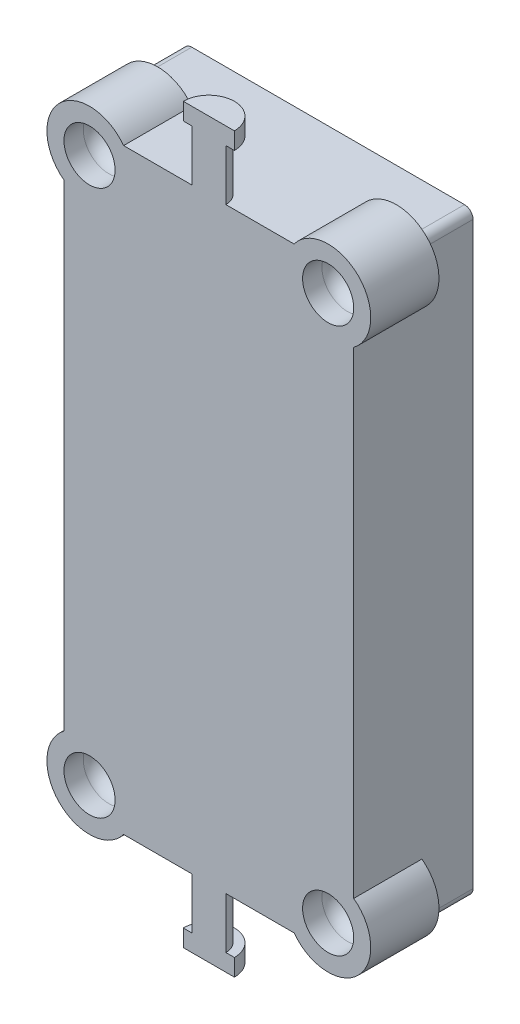
SolidWorks part; units mm, degrees
ref_plane "Front Plane" through (0, 0, 0) normal (0, 0, 1) x (1, 0, 0)
ref_plane "Top Plane" through (0, 0, 0) normal (0, 1, 0) x (1, 0, 0)
ref_plane "Right Plane" through (0, 0, 0) normal (1, 0, 0) x (0, 0, -1)
sketch "Sketch1" plane through (0, 0, 0) normal (0, 0, 1) x (1, 0, 0)
  line L5 (0, 0) -> (34, 0)
  line L6 (0, 0) -> (0, 70)
  line L7 (0, 70) -> (34, 70)
  line L8 (34, 0) -> (34, 70)
  dimension "D1" = 34
  dimension "D2" = 70
extrude "Boss-Extrude1" add sketch "Sketch1" along normal blind 14
sketch "Sketch2" plane through (0, 0, 0) normal (0, 0, -1) x (-1, 0, 0)
  line L0 (-34, 70) -> (0, 70) construction
  line L1 (-32, 68) -> (-2, 68)
  line L2 (-32, 68) -> (-32, 2)
  line L3 (-32, 2) -> (-2, 2)
  line L4 (-2, 68) -> (-2, 2)
  line L5 (0, 70) -> (0, 0) construction
  line L6 (-34, 0) -> (-34, 70) construction
  point P4 (-17, 68)
  point P7 (-17, 70)
  point P8 (-2, 35)
  point P11 (0, 35)
  dimension "D1" = 2
  dimension "D2" = 2
extrude "Cut-Extrude1" cut sketch "Sketch2" against normal offset from surface (12 mm away) 2 up to face at (17, 35, 14)
sketch "Sketch3" plane through (0, 0, 0) normal (0, 0, -1) x (-1, 0, 0)
  line L0 (-34, 70) -> (0, 70) construction
  line L1 (-34, 0) -> (-34, 70) construction
  line L2 (0, 70) -> (0, 0) construction
  line L3 (0, 0) -> (-34, 0) construction
  circle A0 centre (-31, 67) radius 3
  circle A1 centre (-3, 67) radius 3
  circle A2 centre (-3, 3) radius 3
  circle A3 centre (-31, 3) radius 3
  point P16 (0, 0)
  point P17 (0, 0)
  point P18 (0, 0)
  point P19 (0, 0)
  dimension "D1" = 6
  dimension "D2" = 6
  dimension "D3" = 6
  dimension "D4" = 6
extrude "Boss-Extrude2" add sketch "Sketch3" against normal up to surface (12 mm away) up to face at (17, 35, 12)
sketch "Sketch4" plane through (0, 0, 0) normal (0, 0, -1) x (-1, 0, 0)
  circle A0 centre (-3, 67) radius 2
  circle A1 centre (-31, 67) radius 2
  circle A2 centre (-3, 3) radius 2
  circle A3 centre (-31, 3) radius 2
  point P11 (-25.4815, 12.863)
  point P12 (0, 0)
  point P13 (0, 0)
  dimension "D1" = 4
  dimension "D2" = 4
  dimension "D3" = 4
  dimension "D4" = 4
extrude "Cut-Extrude2" cut sketch "Sketch4" against normal through all
sketch "Sketch6" plane through (0, 0, 0) normal (0, -1, 0) x (1, 0, 0)
  line L0 (9.5, 0) -> (24.5, 0) construction
  line L1 (0, 0) -> (34, 0) construction
  circle A0 centre (9.5, 0) radius 2.5
  circle A1 centre (24.5, 0) radius 2
  point P5 (17, 0)
  point P6 (17, 0)
  dimension "D1" = 5
  dimension "D2" = 4
  dimension "D3" = 15
extrude "Cut-Extrude4" cut sketch "Sketch6" against normal up to next
fillet "Fillet1" radius 1 4 edges at (34, 70, 7) (0, 70, 7) (0, 0, 7) (34, 0, 7)
sketch "Sketch7" plane through (0, 0, 14) normal (0, 0, 1) x (1, 0, 0)
  circle A0 centre (31, 67) radius 3
  circle A1 centre (3, 67) radius 3
  circle A2 centre (3, 3) radius 3
  circle A3 centre (31, 3) radius 3
  circle A4 centre (31, 67) radius 5
  circle A5 centre (3, 67) radius 5
  circle A6 centre (31, 3) radius 5
  circle A7 centre (3, 3) radius 5
  dimension "D1" = 6
  dimension "D2" = 6
  dimension "D3" = 6
  dimension "D4" = 6
  dimension "D5" = 10
  dimension "D6" = 10
  dimension "D7" = 10
  dimension "D8" = 10
extrude "Boss-Extrude3" add sketch "Sketch7" against normal offset from surface (8 mm away) 6 up to face at (16.95, 28.2, 0)
sketch "Sketch8" plane through (0, 0, 14) normal (0, 0, 1) x (1, 0, 0)
  circle A0 centre (3, 3) radius 3
  circle A1 centre (31, 3) radius 3
  circle A2 centre (31, 67) radius 3
  circle A4 centre (3, 67) radius 3
  dimension "D1" = 6
  dimension "D2" = 6
  dimension "D3" = 6
  dimension "D4" = 6
extrude "Cut-Extrude7" cut sketch "Sketch8" against normal offset from surface (4 mm away) 10 up to face at (16.95, 28.2, 0)
sketch "Sketch9" plane through (0, 70, 0) normal (0, 1, 0) x (1, 0, 0)
  line L0 (27, -14) -> (7, -14) construction
  line L1 (20, -14) -> (14, -14)
  arc A2 (14, -14) -> (20, -14) centre (17, -14) cw
  dimension "D1" = 3
extrude "Boss-Extrude4" add sketch "Sketch9" along normal blind 8
sketch "Sketch10" plane through (0, 78, 0) normal (0, 1, 0) x (1, 0, 0)
  line L1 (14, -14) -> (20, -14) construction
  line L2 (19, -14) -> (20, -14)
  line L3 (15, -14) -> (14, -14)
  arc A0 (14, -14) -> (20, -14) centre (17, -14) cw
  arc A2 (15, -14) -> (19, -14) centre (17, -14) cw
  dimension "D1" = 1
extrude "Cut-Extrude8" cut sketch "Sketch10" against normal up to surface (8 mm away) from offset 2 up to face at (17, 70, 7.7) offset against normal yes
sketch "Sketch11" plane through (0, 0, 0) normal (0, -1, 0) x (1, 0, 0)
  line L0 (7, 14) -> (27, 14) construction
  line L1 (20, 14) -> (14, 14)
  arc A0 (20, 14) -> (14, 14) centre (17, 14) cw
  dimension "D1" = 3
extrude "Boss-Extrude5" add sketch "Sketch11" along normal blind 8
sketch "Sketch12" plane through (0, -8, 0) normal (0, -1, 0) x (1, 0, 0)
  line L0 (20, 14) -> (14, 14) construction
  line L1 (14, 14) -> (15, 14)
  line L2 (19, 14) -> (20, 14)
  arc A0 (15, 14) -> (19, 14) centre (17, 14) ccw
  arc A1 (20, 14) -> (14, 14) centre (17, 14) cw
  arc A2 (14, 14) -> (20, 14) centre (17, 14) ccw construction
  dimension "D1" = 1
extrude "Cut-Extrude9" cut sketch "Sketch12" against normal up to surface (8 mm away) from offset 2 up to face at (17, 0, 5.8214) offset against normal yes
fillet "Fillet3" radius 2 4 edges at (28, 67, 10) (0, 67, 10) (0, 3, 10) (28, 3, 10)
